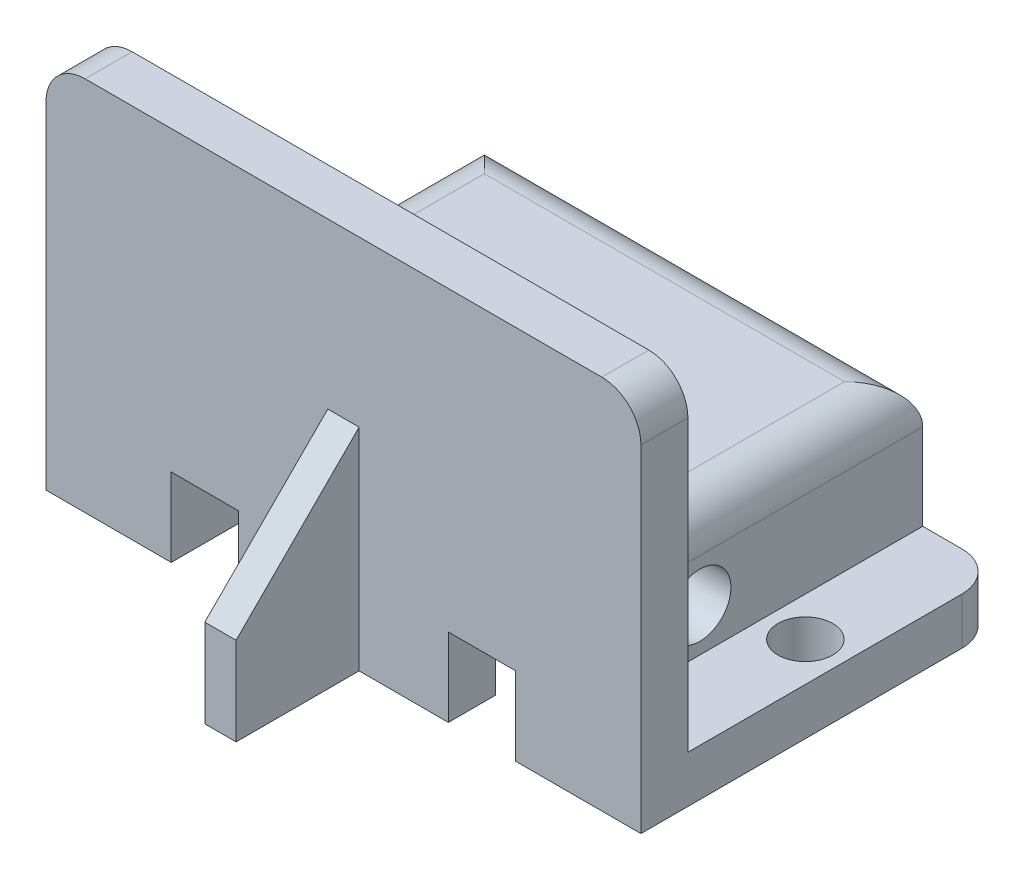
SolidWorks part; units mm, degrees
ref_plane "Front Plane" through (0, 0, 0) normal (0, 0, 1) x (1, 0, 0)
ref_plane "Top Plane" through (0, 0, 0) normal (0, 1, 0) x (1, 0, 0)
ref_plane "Right Plane" through (0, 0, 0) normal (1, 0, 0) x (0, 0, -1)
sketch "Sketch1" plane through (0, 0, 0) normal (1, 0, 0) x (0, 0, -1)
  line L1 (0, 0) -> (3, 0)
  line L2 (0, 0) -> (0, 24)
  line L3 (0, 24) -> (3, 24)
  line L4 (3, 0) -> (3, 24)
  dimension "D1" = 3
  dimension "D2" = 24
extrude "Boss-Extrude1" add sketch "Sketch1" along normal blind 38
sketch "Sketch2" plane through (0, 0, 0) normal (0, 0, 1) x (1, 0, 0)
  line L0 (38, 0) -> (0, 0) construction
  line L1 (18, 0) -> (20, 0)
  line L2 (18, 0) -> (18, 13.4839)
  line L3 (18, 13.4839) -> (20, 13.4839)
  line L4 (20, 0) -> (20, 13.4839)
  line L5 (38, 24) -> (0, 24) construction
  point P6 (19, 24)
  point P7 (19, 13.4839)
  dimension "D1" = 2
extrude "Boss-Extrude2" add sketch "Sketch2" along normal blind 20
chamfer "Chamfer1" distance 20 angle 45 1 edges at (19, 13.4839, 20)
sketch "Sketch3" plane through (0, 0, -3) normal (0, 0, -1) x (-1, 0, 0)
  line L0 (0, 0) -> (0, 24) construction
  line L1 (-38, 3) -> (0, 3)
  line L2 (-38, 3) -> (-38, 0)
  line L3 (-38, 0) -> (0, 0)
  line L4 (0, 3) -> (0, 0)
  line L5 (-38, 0) -> (0, 0) construction
  dimension "D1" = 3
extrude "Boss-Extrude3" add sketch "Sketch3" along normal blind 20
sketch "Sketch4" plane through (0, 0, 0) normal (0, -1, 0) x (1, 0, 0)
  line L0 (38, -23) -> (0, -23) construction
  line L1 (0, -23) -> (0, 0) construction
  line L2 (38, -23) -> (38, 0) construction
  circle A0 centre (2.5, -13) radius 1.75
  circle A1 centre (35.5, -13) radius 1.75
  dimension "D1" = 3.5
  dimension "D2" = 10
  dimension "D3" = 2.5
  dimension "D4" = 2.5
extrude "Cut-Extrude1" cut sketch "Sketch4" against normal through all
sketch "Sketch5" plane through (0, 3, 0) normal (0, 1, 0) x (1, 0, 0)
  line L0 (0, 23) -> (38, 23) construction
  line L1 (5, 23) -> (33, 23)
  line L2 (5, 23) -> (5, 3)
  line L3 (5, 3) -> (33, 3)
  line L4 (33, 23) -> (33, 3)
  line L5 (38, 3) -> (0, 3) construction
  circle A0 centre (2.5, 13) radius 1.75 construction
  circle A1 centre (35.5, 13) radius 1.75 construction
  dimension "D1" = 2.5
  dimension "D2" = 2.5
extrude "Boss-Extrude4" add sketch "Sketch5" along normal blind 8
sketch "Sketch6" plane through (0, 0, 0) normal (0, -1, 0) x (1, 0, 0)
  line L0 (11, -23) -> (27, -23)
  line L2 (27, -23) -> (27, -20)
  line L3 (27, -20) -> (30, -20)
  line L4 (30, -20) -> (30, -3)
  line L5 (30, -3) -> (8, -3)
  line L6 (8, -3) -> (8, -20)
  line L7 (8, -20) -> (11, -20)
  line L8 (11, -20) -> (11, -23)
  line L9 (20, 0) -> (18, 0) construction
  line L10 (33, -3) -> (33, -23) construction
  line L11 (5, -23) -> (5, -3) construction
  line L12 (0, -3) -> (5, -3) construction
  line L14 (38, -23) -> (0, -23) construction
  point P8 (19, 0)
  point P11 (19, -23)
  dimension "D1" = 16
  dimension "D2" = 3
  dimension "D3" = 3
  dimension "D4" = 3
extrude "Cut-Extrude2" cut sketch "Sketch6" against normal offset from surface (8 mm away) 3 up to face at (19, 11, -13)
sketch "Sketch7" plane through (0, 0, -3) normal (0, 0, -1) x (-1, 0, 0)
  line L0 (-30, 0) -> (-8, 0) construction
  line L1 (-30, 0) -> (-25.7004, 0)
  line L2 (-30, 0) -> (-30, 5.0023)
  line L3 (-30, 5.0023) -> (-25.7004, 5.0023)
  line L4 (-25.7004, 0) -> (-25.7004, 5.0023)
  line L5 (-30, 8) -> (-30, 0) construction
  line L6 (-12.2996, 0) -> (-8, 0)
  line L7 (-12.2996, 0) -> (-12.2996, 5.0023)
  line L8 (-12.2996, 5.0023) -> (-8, 5.0023)
  line L9 (-8, 0) -> (-8, 5.0023)
  line L10 (-8, 8) -> (-8, 0) construction
extrude "Cut-Extrude3" cut sketch "Sketch7" against normal blind 15
sketch "Sketch8" plane through (18, 0, 0) normal (-1, 0, 0) x (0, 0, 1)
  line L0 (7.8583, 5.6256) -> (7.8583, 0)
  line L1 (13.4839, 0) -> (0, 13.4839) construction
  line L2 (13.4839, 0) -> (0, 0) construction
  line L3 (7.8583, 0) -> (13.4839, 0)
  line L4 (13.4839, 0) -> (7.8583, 5.6256)
extrude "Cut-Extrude4" cut sketch "Sketch8" against normal blind 15
fillet "Fillet3" radius 2.5 8 edges at (33, 7, -3) (5, 7, -3) (19, 11, -23) (33, 11, -13) (19, 11, -3) (5, 11, -13) (0, 1.5, -23) (38, 1.5, -23)
sketch "Sketch9" plane through (0, 11, 0) normal (0, 1, 0) x (1, 0, 0)
  line L0 (38, 3) -> (0, 3) construction
  line L1 (11, 3) -> (14, 3)
  line L2 (11, 3) -> (11, 13)
  line L3 (11, 13) -> (14, 13)
  line L4 (14, 3) -> (14, 13)
  line L5 (7.5, 20.5) -> (7.5, 5.5) construction
  line L6 (27, 3) -> (24, 3)
  line L7 (27, 3) -> (27, 13)
  line L8 (27, 13) -> (24, 13)
  line L9 (24, 3) -> (24, 13)
  line L10 (30.5, 5.5) -> (30.5, 20.5) construction
  dimension "D1" = 3
  dimension "D2" = 3.5
  dimension "D3" = 3.5
  dimension "D4" = 10
extrude "Boss-Extrude5" add sketch "Sketch9" along normal blind 7.5
chamfer "Chamfer2" distance 7.5 angle 45 2 edges at (12.5, 18.5, -13) (25.5, 18.5, -13)
fillet "Fillet4" radius 2.5 2 edges at (38, 24, -1.5) (0, 24, -1.5)
sketch "Sketch11" plane through (33, 0, 0) normal (1, 0, 0) x (0, 0, -1)
  line L1 (5.5, 8.5) -> (5.5, 3) construction
  circle A0 centre (8.7488, 5.75) radius 2
  point P2 (8.7488, 5.75)
  point P3 (0, 0)
  point P6 (5.5, 5.75)
  point P7 (0, 0)
  dimension "D1" = 4
extrude "Cut-Extrude5" cut sketch "Sketch11" against normal through all
